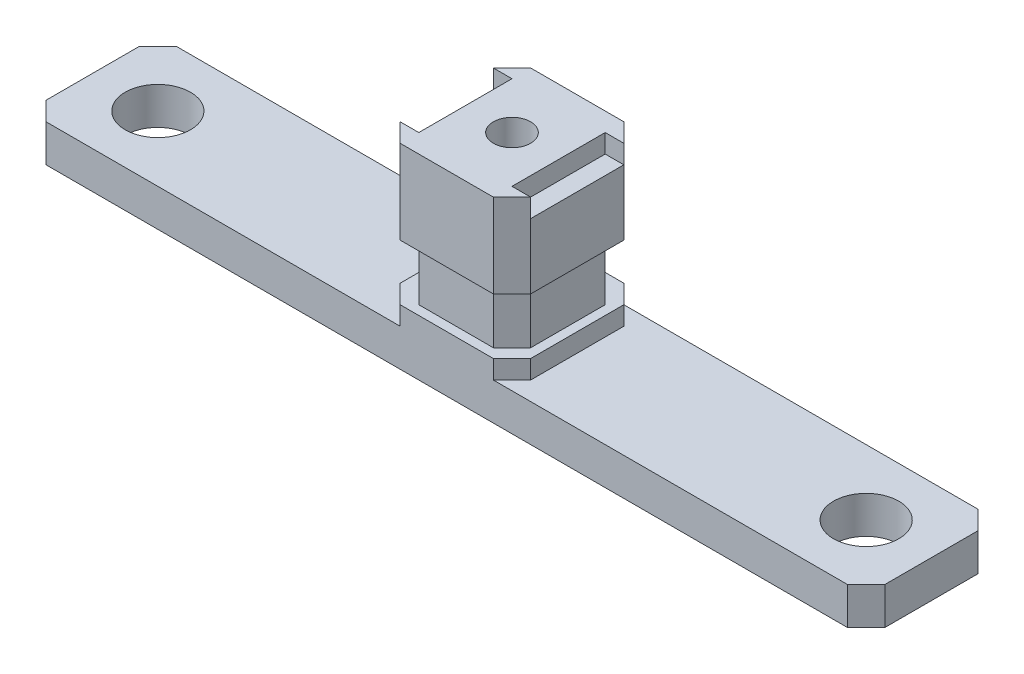
SolidWorks part; units mm, degrees
ref_plane "前视基准面" through (0, 0, 0) normal (0, 0, 1) x (1, 0, 0)
ref_plane "上视基准面" through (0, 0, 0) normal (0, 1, 0) x (1, 0, 0)
ref_plane "右视基准面" through (0, 0, 0) normal (1, 0, 0) x (0, 0, -1)
sketch "草图1" plane through (0, 0, 0) normal (0, 1, 0) x (1, 0, 0)
  line L1 (-45, 7) -> (45, 7)
  line L2 (-45, 7) -> (-45, -7)
  line L3 (-45, -7) -> (45, -7)
  line L4 (45, 7) -> (45, -7)
  line L5 (-45, 7) -> (45, -7) construction
  line L6 (-45, -7) -> (45, 7) construction
  point P0 (0, 0)
  dimension "D1" = 14
  dimension "D2" = 90
extrude "凸台-拉伸1" add sketch "草图1" along normal blind 4
chamfer "倒角1" distance 2 angle 45 4 edges at (-45, 2, -7) (45, 2, 7) (45, 2, -7) (-45, 2, 7)
sketch "草图2" plane through (0, 4, 0) normal (0, 1, 0) x (1, 0, 0)
  line L0 (-43, -7) -> (43, -7) construction
  line L1 (-7, 7) -> (7, 7)
  line L2 (-7, 7) -> (-7, -7)
  line L3 (-7, -7) -> (7, -7)
  line L4 (7, 7) -> (7, -7)
  line L5 (-7, 7) -> (7, -7) construction
  line L6 (-7, -7) -> (7, 7) construction
  point P0 (0, 0)
  dimension "D1" = 14
extrude "凸台-拉伸2" add sketch "草图2" along normal blind 17
sketch "草图3" plane through (0, 4, 0) normal (0, 1, 0) x (1, 0, 0)
  line L1 (-6, 6) -> (6, 6)
  line L2 (-6, 6) -> (-6, -6)
  line L3 (-6, -6) -> (6, -6)
  line L4 (6, 6) -> (6, -6)
  line L5 (-6, 6) -> (6, -6) construction
  line L6 (-6, -6) -> (6, 6) construction
  point P0 (0, 0)
  dimension "D1" = 12
extrude "切除-拉伸1" cut sketch "草图3" along normal blind 6 from offset 2 flip side to cut
chamfer "倒角2" distance 2 angle 45 12 edges at (-7, 16.5, -7) (-6, 9, -6) (-7, 5, -7) (-7, 16.5, 7) (-6, 9, 6) (-7, 5, 7) (7, 5, 7) (7, 5, -7) (7, 16.5, -7) (7, 16.5, 7) (6, 9, 6) (6, 9, -6)
sketch "草图4" plane through (0, 21, 0) normal (0, 1, 0) x (1, 0, 0)
  line L0 (-7, 5) -> (-7, -5) construction
  line L1 (-7, 5) -> (-5, 5)
  line L2 (-7, 5) -> (-7, -5)
  line L3 (-7, -5) -> (-5, -5)
  line L4 (-5, 5) -> (-5, -5)
  line L5 (-5, 0) -> (0, 0) construction
  dimension "D1" = 2
  dimension "D2" = 10
extrude "凸台-拉伸3" add sketch "草图4" along normal blind 2
mirror "镜向1" about plane through (0, 0, 0) normal (1, 0, 0) of "凸台-拉伸3"
sketch "草图5" plane through (0, 21, 0) normal (0, 1, 0) x (1, 0, 0)
  circle A0 centre (0, 0) radius 2
  dimension "D1" = 4
extrude "切除-拉伸2" cut sketch "草图5" against normal through all both and the other way through all
sketch "草图6" plane through (0, 0, 0) normal (0, -1, 0) x (1, 0, 0)
  circle A0 centre (0, 0) radius 4
  dimension "D1" = 8
extrude "切除-拉伸3" cut sketch "草图6" against normal up to surface (12 mm away) and the other way through all up to face at (0, 12, 0)
chamfer "倒角3" distance 2 angle 45 1 edges at (0, 12, 2)
sketch "草图7" plane through (0, 4, 0) normal (0, 1, 0) x (1, 0, 0)
  line L0 (-45, 5) -> (-45, -5) construction
  circle A0 centre (-38, 0) radius 3.5
  dimension "D1" = 7
  dimension "D2" = 7
extrude "切除-拉伸4" cut sketch "草图7" against normal through all both and the other way through all
mirror "镜向2" about plane through (0, 0, 0) normal (1, 0, 0) of "切除-拉伸4"
sketch "草图8" plane through (0, 23, 0) normal (0, 1, 0) x (1, 0, 0)
  line L4 (7, -5) -> (7, 5)
  line L5 (7, 5) -> (5, 5)
  line L6 (5, 5) -> (5, -5)
  line L7 (5, -5) -> (7, -5)
  line L8 (7, -5) -> (7, 5)
  line L9 (7, 5) -> (5, 5)
  line L10 (5, 5) -> (5, -5)
  line L11 (5, -5) -> (7, -5)
  line L12 (-7, 5) -> (-7, -5)
  line L13 (-7, -5) -> (-5, -5)
  line L14 (-5, -5) -> (-5, 5)
  line L15 (-5, 5) -> (-7, 5)
  line L16 (-7, 5) -> (-7, -5)
  line L17 (-7, -5) -> (-5, -5)
  line L18 (-5, -5) -> (-5, 5)
  line L19 (-5, 5) -> (-7, 5)
  dimension "D1" = 0
  dimension "D2" = 0
extrude "切除-拉伸5" cut sketch "草图8" against normal blind 4 and the other way through all
